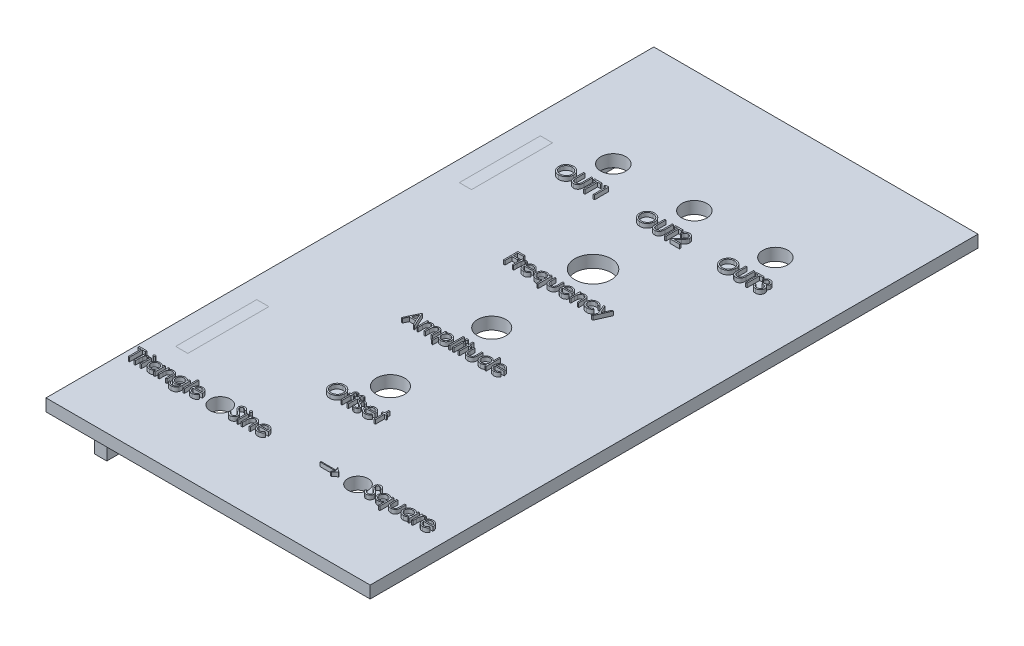
SolidWorks part; units mm, degrees
ref_plane "Front Plane" through (0, 0, 0) normal (0, 0, 1) x (1, 0, 0)
ref_plane "Top Plane" through (0, 0, 0) normal (0, 1, 0) x (1, 0, 0)
ref_plane "Right Plane" through (0, 0, 0) normal (1, 0, 0) x (0, 0, -1)
sketch "Sketch1" plane through (0, 0, 0) normal (0, 1, 0) x (1, 0, 0)
  line L0 (43.5416, -130) -> (50043.5416, -130) construction
  line L1 (0, 0) -> (80, 0)
  line L2 (0, 0) -> (0, -150)
  line L3 (0, -150) -> (80, -150)
  line L4 (80, 0) -> (80, -150)
  line L5 (40, 0.0245) -> (40, -49999.9755) construction
  line L6 (0, -30) -> (50000, -30) construction
  line L8 (5, -33) -> (8, -33)
  line L9 (5, -33) -> (5, -53)
  line L10 (5, -53) -> (8, -53)
  line L11 (8, -33) -> (8, -53)
  line L12 (5, -103) -> (8, -103)
  line L13 (5, -103) -> (5, -123)
  line L14 (5, -123) -> (8, -123)
  line L15 (8, -103) -> (8, -123)
  circle A0 centre (57, -130) radius 2.5
  circle A1 centre (23, -130) radius 2.5
  circle A2 centre (40, -55) radius 4.5
  circle A3 centre (40, -80) radius 3.5
  circle A4 centre (40, -105) radius 3.5
  circle A5 centre (60, -30) radius 3.1
  circle A6 centre (40, -30) radius 3.1
  circle A7 centre (20, -30) radius 3.1
  point P13 (40, 0)
  dimension "D2" = 6.2
  dimension "D11" = 9
  dimension "D13" = 7
  dimension "D14" = 7
  dimension "D15" = 5
  dimension "D1" = 150
  dimension "D3" = 20
  dimension "D4" = 30
  dimension "D5" = 17
  dimension "D6" = 17
  dimension "D7" = 80
  dimension "D8" = 20
  dimension "D9" = 20
  dimension "D10" = 25
  dimension "25" = 25
  dimension "D12" = 25
  dimension "D16" = 20
  dimension "D17" = 20
  dimension "D18" = 3
  dimension "D19" = 3
  dimension "D20" = 5
  dimension "D21" = 5
  dimension "D22" = 27
  dimension "D23" = 50
extrude "Boss-Extrude1" add sketch "Sketch1" along normal blind 3
ref_plane "Plane1" through (5, 0, 0) normal (1, 0, 0) x (0, 0, -1)
sketch "Sketch2" plane through (5, 0, 0) normal (1, 0, 0) x (0, 0, -1)
  line L0 (-14.476, 0) -> (-14.476, -10)
  line L1 (-14.476, -10) -> (-143, -10)
  line L2 (-143, -10) -> (-143, 0)
  line L3 (-143, 0) -> (-123, 0)
  line L4 (-123, 0) -> (-123, 3)
  line L5 (-123, 3) -> (-103, 3)
  line L6 (-103, 3) -> (-103, 0)
  line L7 (-103, 0) -> (-53, 0)
  line L8 (-53, 0) -> (-53, 3)
  line L9 (-53, 3) -> (-33, 3)
  line L10 (-33, 3) -> (-33, 0)
  line L11 (-33, 0) -> (-14.476, 0)
  line L13 (-150, 3) -> (-150, 0) construction
  line L15 (-149.0657, -3) -> (49850.9343, -3) construction
  circle A0 centre (-140.33, -3) radius 1.6
  circle A1 centre (-17.13, -3) radius 1.6
  circle A2 centre (-54.6, -3) radius 1.6
  circle A3 centre (-96.26, -3) radius 1.6
  dimension "D9" = 3.2
  dimension "D10" = 37.47
  dimension "D11" = 2.67
  dimension "D1" = 128.524
  dimension "D2" = 20
  dimension "D3" = 20
  dimension "D4" = 50
  dimension "D5" = 3
  dimension "D6" = 7
  dimension "D7" = 10
  dimension "D8" = 20
  dimension "D12" = 3
  dimension "D13" = 44.07
  dimension "D14" = 41.66
extrude "Boss-Extrude2" add sketch "Sketch2" along normal blind 3 separate body
sketch "Sketch3" plane through (0, 3, 0) normal (0, 1, 0) x (1, 0, 0)
  line L0 (8, -53) -> (8, -33) construction
  line L1 (80, 0) -> (0, 0) construction
  line L2 (0, 0) -> (0, -150) construction
  line L3 (0, -150) -> (80, -150) construction
  text T0 "OUT1"
  text T1 "OUT2"
  text T2 "OUT3"
  text T3 "Frequency\r\n"
  text T4 "Amplitude"
  text T5 "Offset"
  text T6 "Triangle     Sine"
  text T7 " →     Square"
  dimension "D1" = 6.5
  dimension "D2" = 40
  dimension "D3" = 20
  dimension "D4" = 40
  dimension "D5" = 20
  dimension "D6" = 40
  dimension "D7" = 27.5
  dimension "D8" = 65
  dimension "D9" = 90
  dimension "D10" = 27.5
  dimension "D11" = 33
  dimension "D12" = 115
  dimension "D13" = 1.5
  dimension "D14" = 18
  dimension "D15" = 47
  dimension "D16" = 18
extrude "Boss-Extrude3" add sketch "Sketch3" along normal blind 1
